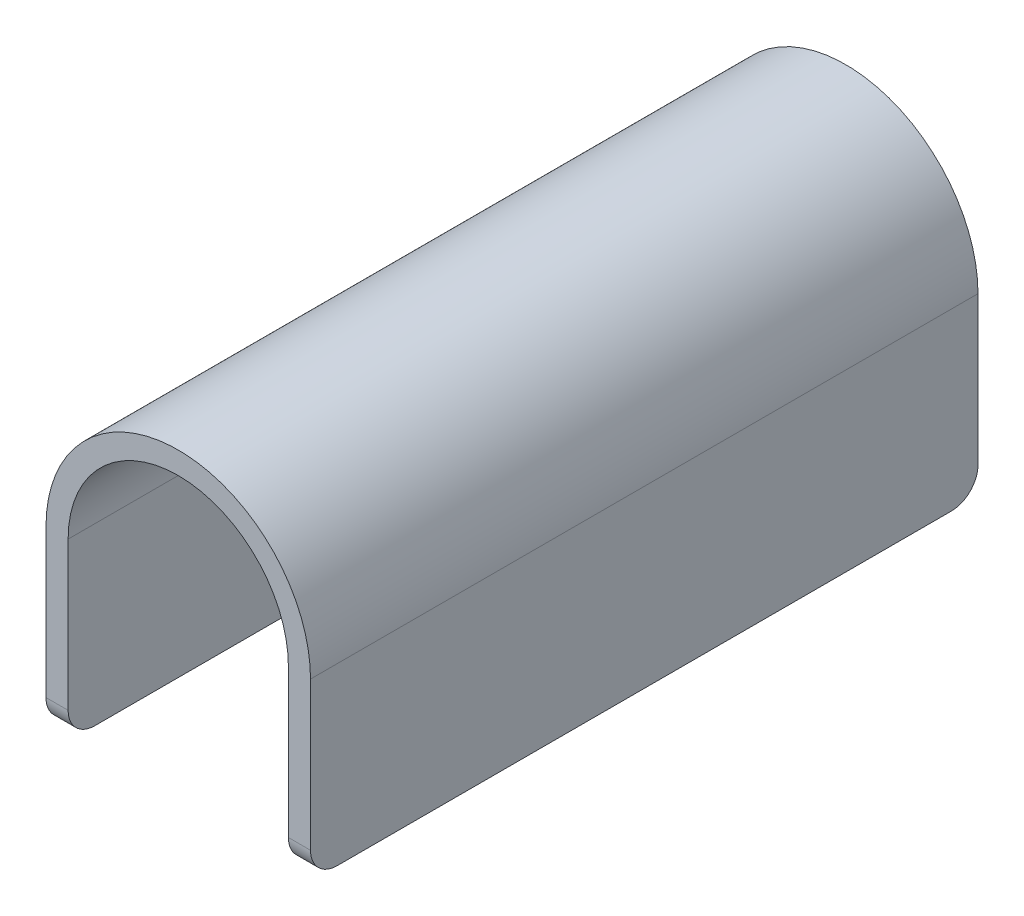
SolidWorks part; units mm, degrees
ref_plane "Piano frontale" through (0, 0, 0) normal (0, 0, 1) x (1, 0, 0)
ref_plane "Piano superiore" through (0, 0, 0) normal (0, 1, 0) x (1, 0, 0)
ref_plane "Piano destro" through (0, 0, 0) normal (1, 0, 0) x (0, 0, -1)
sketch "Schizzo1" plane through (0, 0, 0) normal (0, 0, 1) x (1, 0, 0)
  line L3 (-39.628, 0) -> (-33, 0)
  line L4 (33, 0) -> (39.628, 0)
  arc A4 (33, 0) -> (-33, 0) centre (0, 0) ccw
  arc A5 (39.628, 0) -> (-39.628, 0) centre (0, 0) ccw
extrude "Estrusione-Estrusione2" add sketch "Schizzo1" along normal blind 200
sketch "Schizzo2" plane through (0, 0, 0) normal (0, 0, 1) x (1, 0, 0)
  line L0 (-39.628, 0) -> (-39.628, -16.4293)
  line L1 (-33, 0) -> (-33, -16.4293)
  line L3 (33, 0) -> (33, -20)
  line L5 (39.628, -16.4293) -> (39.628, 0)
  line L6 (39.628, 0) -> (33, 0)
  line L7 (-39.628, 0) -> (-33, 0)
  line L8 (-39.628, -16.4293) -> (-39.628, -52.4293)
  line L9 (-39.628, -52.4293) -> (-33, -52.4293)
  line L10 (-33, -52.4293) -> (-33, -16.4293)
  line L11 (33, -20) -> (33, -52.4293)
  line L12 (33, -52.4293) -> (39.628, -52.4293)
  line L13 (39.628, -52.4293) -> (39.628, -16.4293)
  dimension "D1" = 36
  dimension "D2" = 36
extrude "Estrusione-Estrusione3" add sketch "Schizzo2" along normal up to vertex (200 mm away) up to point (-39.628, 0, 200)
fillet "Raccordo1" radius 8 4 edges at (36.314, -52.4293, 0) (-36.314, -52.4293, 0) (-36.314, -52.4293, 200) (36.314, -52.4293, 200)
